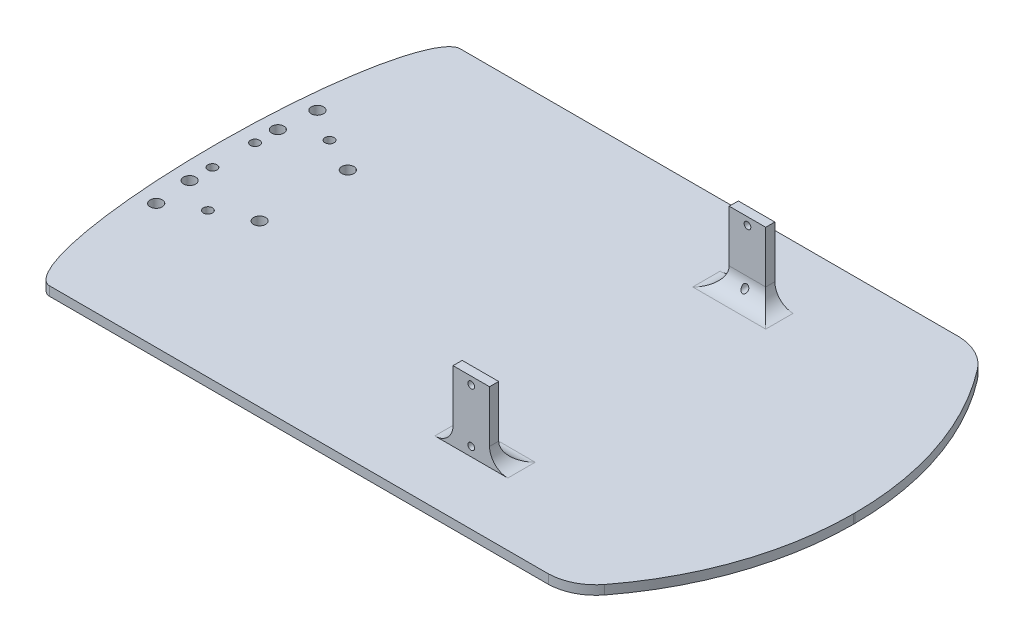
SolidWorks part; units mm, degrees
ref_plane "Front Plane" through (0, 0, 0) normal (0, 0, 1) x (1, 0, 0)
ref_plane "Top Plane" through (0, 0, 0) normal (0, 1, 0) x (1, 0, 0)
ref_plane "Right Plane" through (0, 0, 0) normal (1, 0, 0) x (0, 0, -1)
sketch "Sketch1" plane through (0, 0, 0) normal (0, 1, 0) x (1, 0, 0)
  line L1 (0, 0) -> (210, 0)
  line L2 (0, 0) -> (0, 149)
  line L3 (0, 149) -> (210, 149)
  line L4 (210, 0) -> (210, 149)
  dimension "D1" = 210
  dimension "D2" = 149
extrude "Boss-Extrude1" add sketch "Sketch1" along normal blind 3
sketch "Sketch2" plane through (0, 3, 0) normal (0, 1, 0) x (1, 0, 0)
  line L0 (210, 149) -> (0, 149) construction
  line L1 (177, 149) -> (0, 149)
  line L2 (177, 149) -> (177, 142)
  line L3 (177, 142) -> (0, 142)
  line L4 (0, 149) -> (0, 142)
  line L5 (0, 149) -> (0, 0) construction
  line L7 (0, 0) -> (177, 0)
  line L8 (0, 0) -> (0, 7)
  line L9 (0, 7) -> (177, 7)
  line L10 (177, 0) -> (177, 7)
  dimension "D1" = 177
  dimension "D2" = 7
  dimension "D3" = 7
extrude "Cut-Extrude1" cut sketch "Sketch2" against normal blind 3
sketch "Sketch3" plane through (0, 3, 0) normal (0, 1, 0) x (1, 0, 0)
  line L0 (0, 142) -> (177, 142) construction
  line L9 (177, 142) -> (177, 149) construction
  line L14 (210, 74.5) -> (0, 74.5) construction
  line L15 (137, 121.4) -> (125, 121.4)
  line L16 (137, 121.4) -> (137, 118.4)
  line L17 (137, 118.4) -> (125, 118.4)
  line L18 (125, 121.4) -> (125, 118.4)
  line L31 (210, 0) -> (210, 149) construction
  line L32 (0, 142) -> (0, 7) construction
  line L45 (125, 27.6) -> (125, 30.6)
  line L46 (137, 30.6) -> (125, 30.6)
  line L47 (137, 27.6) -> (137, 30.6)
  line L48 (137, 27.6) -> (125, 27.6)
  dimension "D2" = 20.6
  dimension "D12" = 3
  dimension "D14" = 12
  dimension "D15" = 40
sketch "Sketch6" plane through (0, 3, 0) normal (0, 1, 0) x (1, 0, 0)
  line L0 (0, 74.5) -> (210, 74.5) construction
  line L1 (0, 142) -> (0, 7) construction
  line L2 (210, 0) -> (210, 149) construction
  line L3 (29, 60) -> (29, 89)
  line L4 (29, 60) -> (6, 60)
  line L5 (29, 89) -> (6, 89)
  line L6 (6, 60) -> (6, 89)
  line L7 (29, 60) -> (6, 89) construction
  line L8 (29, 89) -> (6, 60) construction
  line L9 (0, 74.5) -> (46.1912, 74.5) construction
  circle A0 centre (6, 89) radius 2
  circle A1 centre (29, 89) radius 2
  circle A2 centre (29, 60) radius 2
  circle A3 centre (6, 60) radius 2
  circle A4 centre (6, 81.5) radius 1.5
  circle A5 centre (6, 67.5) radius 1.5
  circle A6 centre (7, 48) radius 2
  circle A7 centre (17.5, 54.5) radius 1.5
  circle A8 centre (17.5, 94.5) radius 1.5
  circle A9 centre (7, 101) radius 2
  point P7 (17.5, 74.5)
  dimension "D4" = 4
  dimension "D5" = 4
  dimension "D6" = 4
  dimension "D7" = 4
  dimension "D8" = 3
  dimension "D9" = 3
  dimension "D12" = 12
  dimension "D14" = 20
  dimension "D1" = 29
  dimension "D2" = 23
  dimension "D3" = 6
  dimension "D10" = 14
  dimension "D11" = 7
  dimension "D13" = 1
extrude "Cut-Extrude6" cut sketch "Sketch6" against normal blind 3 contours A9 | A8 | A0 | A1 | A2 | A4 | A5 | A3 | A7 | A6
sketch "Sketch12" plane through (0, 3, 0) normal (0, 1, 0) x (1, 0, 0)
  line L0 (0, 142) -> (177, 142) construction
  line L1 (13, 142) -> (0, 142)
  line L2 (0, 142) -> (0, 74.5)
  line L3 (0, 142) -> (0, 7) construction
  line L4 (0, 74.5) -> (0, 7)
  line L5 (0, 7) -> (13, 7)
  ellipse E0 centre (13, 74.5) end of major axis (13, 142) minor radius 13
  dimension "D1" = 13
extrude "Cut-Extrude10" cut sketch "Sketch12" against normal blind 3 contours E0 L1 L2 | E0 L4 L5 region at (2.9038, 3, -126.9227) region at (2.9038, 3, -22.0773)
extrude "Ressalto-extrusão1" add sketch "Sketch3" along normal blind 23
sketch "Esboço4" plane through (0, 0, -27.6) normal (0, 0, 1) x (1, 0, 0)
  line L0 (131, 26) -> (131, 3) construction
  line L1 (125, 26) -> (137, 26) construction
  line L2 (125, 3) -> (137, 3) construction
  circle A0 centre (131, 23.5) radius 1.1
  circle A1 centre (131, 6) radius 1.1
  dimension "D1" = 2.2
  dimension "D2" = 20.5
  dimension "D3" = 3
extrude "Corte-extrusão1" cut sketch "Esboço4" against normal through all
fillet "Filete3" radius 6 6 edges at (137, 3, -29.1) (125, 3, -29.1) (131, 3, -30.6) (125, 3, -119.9) (137, 3, -119.9) (131, 3, -118.4)
fillet "Filete6" radius 100 2 edges at (210, 1.5, 0) (210, 1.5, -149)
fillet "Filete7" radius 16 2 edges at (177, 1.5, -149) (177, 1.5, 0)
